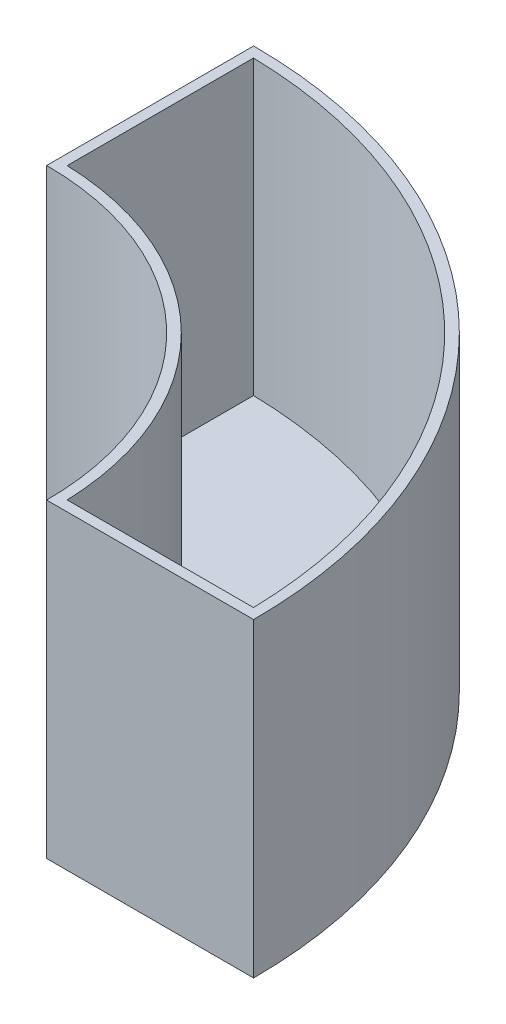
SolidWorks part; units mm, degrees
ref_plane "Piano frontale" through (0, 0, 0) normal (0, 0, 1) x (1, 0, 0)
ref_plane "Piano superiore" through (0, 0, 0) normal (0, 1, 0) x (1, 0, 0)
ref_plane "Piano destro" through (0, 0, 0) normal (1, 0, 0) x (0, 0, -1)
sketch "Schizzo1" plane through (0, 0, 0) normal (0, 1, 0) x (1, 0, 0)
  line L0 (0, 0) -> (0, 112) construction
  line L1 (0, 0) -> (112, 0) construction
  line L2 (0, 112) -> (0, 192)
  line L3 (112, 0) -> (192, 0)
  arc A0 (112, 0) -> (0, 112) centre (0, 0) ccw
  arc A1 (192, 0) -> (0, 192) centre (0, 0) ccw
  dimension "D1" = 112
  dimension "D2" = 80
extrude "Estrusione-Estrusione1" add sketch "Schizzo1" along normal blind 120
sketch "Schizzo2" plane through (0, 120, 0) normal (0, 1, 0) x (1, 0, 0)
  line L0 (4, 115.931) -> (4, 187.9574)
  line L1 (115.931, 4) -> (187.9574, 4)
  line L2 (0, 192) -> (0, 112) construction
  line L3 (112, 0) -> (192, 0) construction
  arc A0 (187.9574, 4) -> (4, 187.9574) centre (0, 0) ccw
  arc A1 (115.931, 4) -> (4, 115.931) centre (0, 0) ccw
  arc A2 (112, 0) -> (0, 112) centre (0, 0) ccw construction
  arc A3 (192, 0) -> (0, 192) centre (0, 0) ccw construction
  dimension "D1" = 4
  dimension "D2" = 4
  dimension "D3" = 4
  dimension "D4" = 4
extrude "Taglio-Estrusione1" cut sketch "Schizzo2" against normal blind 113
sketch "Schizzo3" plane through (0, 0, 0) normal (0, -1, 0) x (1, 0, 0)
  line L0 (0, 0) -> (192, 0) construction
  line L1 (0, 0) -> (0, -192) construction
  line L2 (0, 0) -> (146.8207, -39.3405) construction
  line L3 (0, 0) -> (39.3405, -146.8207) construction
  line L4 (34.4896, -148.0354) -> (24.1292, -109.3699)
  line L5 (44.1488, -145.4472) -> (33.7885, -106.7817)
  line L6 (145.4472, -44.1488) -> (106.7817, -33.7885)
  line L7 (148.0354, -34.4896) -> (109.3699, -24.1292)
  arc A0 (0, -192) -> (192, 0) centre (0, 0) ccw construction
  arc A1 (24.1292, -109.3699) -> (33.7885, -106.7817) centre (0, 0) ccw
  arc A3 (44.5795, -186.753) -> (49.6933, -185.4578) centre (0, 0) ccw
  arc A4 (184.0226, -54.7695) -> (186.753, -44.5795) centre (0, 0) ccw
  arc A5 (106.7817, -33.7885) -> (109.3699, -24.1292) centre (0, 0) ccw
  arc A6 (0, -112) -> (112, 0) centre (0, 0) ccw construction
  arc A7 (145.4472, -44.1488) -> (148.0354, -34.4896) centre (0, 0) ccw
  arc A8 (34.4896, -148.0354) -> (44.1488, -145.4472) centre (0, 0) ccw
  dimension "D3" = 40
  dimension "D1" = 15
  dimension "D2" = 15
  dimension "D4" = 5
  dimension "D5" = 10
  dimension "D6" = 5
  dimension "D7" = 10
extrude "Taglio-Estrusione2" cut sketch "Schizzo3" against normal blind 5 contours L5 A1 L4 A8 | L7 A5 L6 A7
fillet "Raccordo1" radius 5 2 edges at (146.8207, 0, -39.3405) (39.3405, 0, -146.8207) conic rho 0.6
